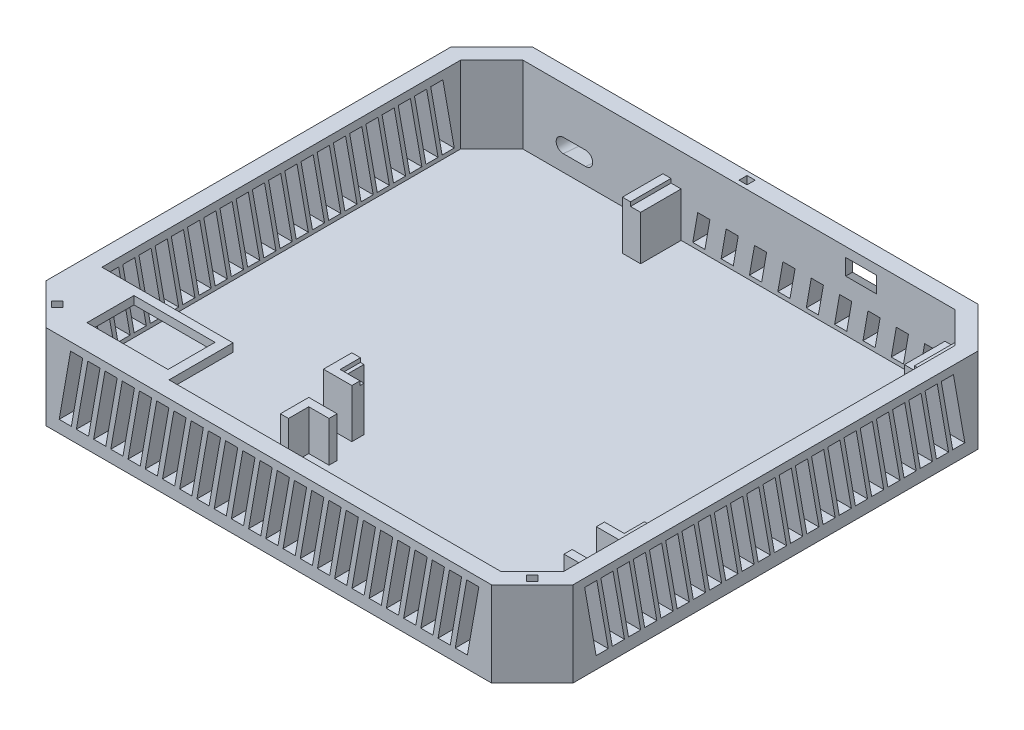
SolidWorks part; units mm, degrees
ref_plane "Front Plane" through (0, 0, 0) normal (0, 0, 1) x (1, 0, 0)
ref_plane "Top Plane" through (0, 0, 0) normal (0, 1, 0) x (1, 0, 0)
ref_plane "Right Plane" through (0, 0, 0) normal (1, 0, 0) x (0, 0, -1)
sketch "Sketch2" plane through (0, 0, 0) normal (0, 1, 0) x (1, 0, 0)
  line L0 (-55, 60) -> (-65, 50)
  line L1 (-55, 60) -> (55, 60)
  line L2 (-65, 50) -> (-65, -50)
  line L3 (-55, -60) -> (55, -60)
  line L4 (65, 50) -> (65, -50)
  line L5 (-65, -50) -> (-55, -60)
  line L6 (55, -60) -> (65, -50)
  line L7 (55, 60) -> (65, 50)
  point P0 (0, 0)
  point P1 (65, -60)
  point P2 (-65, 60)
  point P3 (-65, -60)
  point P4 (65, 60)
  point P14 (0, 60)
  point P15 (65, 0)
  dimension "D1" = 120
  dimension "D2" = 110
extrude "Boss-Extrude1" add sketch "Sketch2" against normal blind 21
shell "Shell3" thickness 4 removed face at (0, 0, 0)
sketch "Sketch3" plane through (0, 0, 0) normal (0, 1, 0) x (1, 0, 0)
  line L0 (55, 60) -> (-55, 60) construction
  line L1 (-1, 59) -> (1, 59)
  line L2 (-1, 59) -> (-1, 57)
  line L3 (-1, 57) -> (1, 57)
  line L4 (1, 59) -> (1, 57)
  line L5 (-1, 59) -> (1, 57) construction
  line L6 (-1, 57) -> (1, 59) construction
  line L7 (53.3431, 56) -> (-53.3431, 56) construction
  line L8 (53.3431, -56) -> (61, -48.3431) construction
  line L9 (57.1716, -53.5858) -> (58.5858, -52.1716)
  line L10 (57.1716, -53.5858) -> (58.5858, -55)
  line L11 (58.5858, -55) -> (60, -53.5858)
  line L12 (58.5858, -52.1716) -> (60, -53.5858)
  line L13 (57.1716, -53.5858) -> (60, -53.5858) construction
  line L14 (58.5858, -55) -> (58.5858, -52.1716) construction
  line L15 (57.1716, -52.1716) -> (60, -55) construction
  line L16 (55, -60) -> (65, -50) construction
  line L17 (0, 60) -> (0, -60) construction
  line L18 (-55, -60) -> (55, -60) construction
  line L19 (-58.5858, -52.1716) -> (-60, -53.5858)
  line L20 (-58.5858, -55) -> (-60, -53.5858)
  line L21 (-57.1716, -53.5858) -> (-58.5858, -52.1716)
  line L22 (-57.1716, -53.5858) -> (-58.5858, -55)
  point P0 (0, 58)
  point P7 (0, 60)
  point P8 (0, 59)
  point P11 (58.5858, -53.5858)
  point P18 (57.8787, -52.8787)
  dimension "D1" = 2
  dimension "D2" = 1
  dimension "D3" = 2
  dimension "D4" = 1
  dimension "D5" = 1
extrude "Cut-Extrude1" cut sketch "Sketch3" against normal blind 2
sketch "Sketch5" plane through (-61, 0, 0) normal (-1, 0, 0) x (0, 0, 1)
  line L0 (-43.9325, -2) -> (-40.9325, -2)
  line L1 (-40.9325, -2) -> (-43.7538, -18)
  line L2 (-43.7538, -18) -> (-46.7538, -18)
  line L3 (-46.7538, -18) -> (-43.9325, -2)
  line L5 (-50, 0) -> (50, 0) construction
  line L7 (-48.3431, -19) -> (-48.3431, 0) construction
  line L8 (-48.3431, -19) -> (48.3431, -19) construction
  point P2 (-45.3431, -10)
  point P11 (-48.3431, -9.5)
  dimension "SLIT_RIGHT_OFFSET" = 3
  dimension "SW" = 3
  dimension "SDS" = 1
  dimension "STS" = 2
  dimension "SA" = 80
extrude "Cut-Extrude3" cut sketch "Sketch5" against normal through all and the other way up to next
pattern_linear "LPattern2" count 23 along (0, 0, 1) of "Cut-Extrude3"
sketch "Sketch4" plane through (0, 0, 56) normal (0, 0, 1) x (1, 0, 0)
  line L0 (-48.9325, -2) -> (-45.9325, -2)
  line L1 (-45.9325, -2) -> (-48.7538, -18)
  line L2 (-48.7538, -18) -> (-51.7538, -18)
  line L3 (-51.7538, -18) -> (-48.9325, -2)
  line L4 (-55, 0) -> (55, 0) construction
  line L7 (-53.3431, -19) -> (53.3431, -19) construction
  line L8 (-53.3431, -19) -> (-53.3431, 0) construction
  point P8 (-50.3431, -10)
  point P11 (-53.3431, -9.5)
  dimension "D1" = 3
  dimension "D2" = 2
  dimension "D3" = 1
  dimension "D4" = 3
  dimension "D5" = 80
extrude "Cut-Extrude2" cut sketch "Sketch4" along normal up to next
pattern_linear "LPattern1" count 24 spacing 4.25 along (1, 0, 0) of "Cut-Extrude2"
sketch "Sketch7" plane through (0, -19, 0) normal (0, 1, 0) x (1, 0, 0)
  line L0 (53.3431, 56) -> (-53.3431, 56) construction
  line L1 (53.3431, 56) -> (-16.7569, 56) construction
  line L2 (53.3431, 56) -> (53.3431, -26.5) construction
  line L3 (53.3431, -26.5) -> (-16.7569, -26.5) construction
  line L4 (-16.7569, 56) -> (-16.7569, -26.5) construction
  line L5 (-18.7569, 56) -> (-18.7569, 46)
  line L6 (-16.878, -20.6506) -> (-15.878, -20.6506)
  line L7 (28.7735, 56) -> (34.3431, 56) construction
  line L8 (28.7735, 56) -> (28.7735, 52.8671) construction
  line L9 (28.7735, 52.8671) -> (34.3431, 52.8671) construction
  line L10 (34.3431, 56) -> (34.3431, 52.8671) construction
  line L11 (28.7735, 56) -> (34.3431, 52.8671) construction
  line L12 (28.7735, 52.8671) -> (34.3431, 56) construction
  line L13 (-18.7569, 46) -> (-14.2569, 46)
  line L16 (-15.878, -20.6506) -> (-15.878, -24.6506)
  line L17 (-15.878, -24.6506) -> (-11.878, -24.6506)
  line L18 (-18.7569, 56) -> (-14.2569, 56)
  line L19 (-14.2569, 56) -> (-14.2569, 46)
  line L20 (-11.878, -24.6506) -> (-11.878, -25.6506)
  line L21 (18.2931, -26.5) -> (18.2931, 56) construction
  line L22 (-18.878, -20.6506) -> (-18.878, -27.6506)
  line L23 (-18.878, -27.6506) -> (-11.878, -27.6506)
  line L24 (-11.878, -27.6506) -> (-11.878, -25.6506)
  line L27 (-16.878, -20.6506) -> (-18.878, -20.6506)
  point P8 (31.5583, 54.4335)
  line M17 (53.3431, 56) -> (-53.3431, 56)
  dimension "D1" = 82.5
  dimension "D2" = 70.1
  dimension "D3" = 3.1329
  dimension "D4" = 5.5696
  dimension "D5" = 19
  dimension "D6" = 2
  dimension "D7" = 2.5
  dimension "D8" = 10
  dimension "D9" = 2
  dimension "D10" = 2
  dimension "D11" = 7
  dimension "D12" = 7
  dimension "D13" = 1
  dimension "D14" = 1
  dimension "D15" = 5.8494
extrude "Boss-Extrude2" add sketch "Sketch7" along normal blind 12 contours L19 L5 L13 M17 | L27 L22 L23 L24 region at (-16.5069, -19, -51) region at (-16.1052, -19, 24.8779)
sketch "Sketch8" plane through (0, -7, 0) normal (0, 1, 0) x (1, 0, 0)
  line L0 (-16.7569, 56) -> (-16.7569, 46)
  line L3 (-16.7569, 46) -> (-14.2569, 46)
  line L4 (-14.2569, 46) -> (-14.2569, 56)
  line L5 (-14.2569, 56) -> (-16.7569, 56)
  line L6 (-16.7569, 56) -> (-16.7569, -26.5) construction
  line L8 (-14.2569, 56) -> (-14.2569, 46) construction
  line L9 (-18.7569, 46) -> (-14.2569, 46) construction
  line L10 (-18.7569, 56) -> (-14.2569, 56) construction
  line L25 (-16.7569, -20.6506) -> (-15.878, -20.6506)
  line L26 (-15.878, -20.6506) -> (-15.878, -24.6506)
  line L27 (-15.878, -24.6506) -> (-11.878, -24.6506)
  line L28 (-11.878, -24.6506) -> (-11.878, -25.6506)
  line L29 (-11.878, -25.6506) -> (-16.7569, -25.6506)
  line L30 (-16.7569, -25.6506) -> (-16.7569, -20.6506)
extrude "Cut-Extrude6" cut sketch "Sketch8" against normal blind 1
ref_plane "Plane3" through (18.2931, 0, 0) normal (-1, 0, 0) x (0, 0, 1)
mirror "Mirror3" about plane through (18.2931, 0, 0) normal (-1, 0, 0) of "Cut-Extrude6", "Boss-Extrude2"
sketch "Sketch9" plane through (0, 0, -56) normal (0, 0, 1) x (1, 0, 0)
  line L0 (53.3431, -7) -> (53.3431, 0) construction
  line L1 (26.3431, -2.34) -> (33.9431, -2.34)
  line L2 (26.3431, -2.34) -> (26.3431, -6.34)
  line L3 (26.3431, -6.34) -> (33.9431, -6.34)
  line L4 (33.9431, -2.34) -> (33.9431, -6.34)
  line L5 (26.3431, -2.34) -> (33.9431, -6.34) construction
  line L6 (26.3431, -6.34) -> (33.9431, -2.34) construction
  line L8 (53.3431, -8) -> (50.8431, -8) construction
  point P0 (30.1431, -4.34)
  dimension "D1" = 4
  dimension "D2" = 7.6
  dimension "D3" = 19.4
  dimension "D4" = 1.66
extrude "Cut-Extrude7" cut sketch "Sketch9" against normal up to next (4 mm away) draft 30 draft outward yes
sketch "Sketch10" plane through (0, -19, 0) normal (0, 1, 0) x (1, 0, 0)
  line L0 (53.3431, -35.5) -> (53.3431, -33.5)
  line L1 (53.3431, -35.5) -> (53.3431, -54) construction
  line L2 (53.3431, -35.5) -> (-14.6569, -35.5) construction
  line L3 (-14.6569, -35.5) -> (-14.6569, -54) construction
  line L4 (53.3431, -54) -> (-14.6569, -54) construction
  line L5 (53.3431, -33.5) -> (48.3431, -33.5)
  line L6 (48.3431, -33.5) -> (48.3431, -35.5)
  line L7 (48.3431, -35.5) -> (53.3431, -35.5)
  line L8 (53.3431, -44.75) -> (-14.6569, -44.75) construction
  line L9 (19.3431, -35.5) -> (19.3431, -54) construction
  line L10 (48.3431, -56) -> (48.3431, -54)
  line L11 (48.3431, -54) -> (53.3431, -54)
  line L12 (53.3431, -56) -> (48.3431, -56)
  line L13 (53.3431, -54) -> (53.3431, -56)
  line L14 (-9.6569, -56) -> (-9.6569, -54)
  line L18 (-9.6569, -54) -> (-14.6569, -54)
  line L19 (-9.6569, -35.5) -> (-14.6569, -35.5)
  line L20 (-16.6569, -33.5) -> (-9.6569, -33.5)
  line L21 (-9.6569, -33.5) -> (-9.6569, -35.5)
  line L22 (-53.3431, -56) -> (53.3431, -56) construction
  line L24 (-16.6569, -33.5) -> (-16.6569, -40.5)
  line L25 (-14.6569, -35.5) -> (-14.6569, -40.5)
  line L26 (-14.6569, -40.5) -> (-16.6569, -40.5)
  line L27 (-16.6569, -56) -> (-16.6569, -49)
  line L28 (-9.6569, -56) -> (-16.6569, -56)
  line L29 (-14.6569, -49) -> (-16.6569, -49)
  line L30 (-14.6569, -54) -> (-14.6569, -49)
  dimension "D3" = 2
  dimension "D1" = 68
  dimension "D2" = 18.5
  dimension "D4" = 2
  dimension "D5" = 7
  dimension "D6" = 2
  dimension "D7" = 5
  dimension "D8" = 7
extrude "Boss-Extrude3" add sketch "Sketch10" along normal blind 10
sketch "Sketch12" plane through (0, 0, 0) normal (0, 1, 0) x (1, 0, 0)
  line L0 (-53.3431, -56) -> (-28.6431, -56)
  line L1 (-53.3431, -56) -> (-16.6569, -56) construction
  line L2 (-28.6431, -56) -> (-28.6431, -40.2)
  line L3 (-28.6431, -40.2) -> (-61, -40.2)
  line L4 (-61, 48.3431) -> (-61, -48.3431) construction
  line L5 (-61, -40.2) -> (-61, -48.3431)
  line L6 (-61, -48.3431) -> (-53.3431, -56)
  line L8 (-50.9931, -42.3) -> (-30.9931, -42.3)
  line L9 (-50.9931, -42.3) -> (-50.9931, -53.9)
  line L10 (-50.9931, -53.9) -> (-30.9931, -53.9)
  line L11 (-30.9931, -42.3) -> (-30.9931, -53.9)
  line L12 (-50.9931, -42.3) -> (-30.9931, -53.9) construction
  line L13 (-50.9931, -53.9) -> (-30.9931, -42.3) construction
  point P9 (-40.9931, -48.1)
  point P16 (-30.9931, -48.1)
  point P17 (-28.6431, -48.1)
  point P18 (-40.9931, -53.9)
  point P19 (-40.9931, -56)
  dimension "D1" = 24.7
  dimension "D2" = 15.8
  dimension "D3" = 11.6
  dimension "D4" = 20
extrude "Boss-Extrude4" add sketch "Sketch12" against normal up to vertex (2 mm away) up to point (-28.9325, -2, 56)
sketch "Sketch13" plane through (0, 0, -56) normal (0, 0, 1) x (1, 0, 0)
  line L0 (-43.3431, -13.25) -> (-37.8431, -13.25) construction
  line L1 (-43.3431, -11.5) -> (-37.8431, -11.5)
  line L2 (-43.3431, -15) -> (-37.8431, -15)
  line L3 (-18.7569, -19) -> (-53.3431, -19) construction
  line L4 (-53.3431, -19) -> (-53.3431, 0) construction
  arc A0 (-43.3431, -11.5) -> (-43.3431, -15) centre (-43.3431, -13.25) ccw
  arc A1 (-37.8431, -15) -> (-37.8431, -11.5) centre (-37.8431, -13.25) ccw
  point P2 (-40.5931, -13.25)
  point P7 (-45.0931, -13.25)
  point P8 (-36.0931, -13.25)
  dimension "D4" = 10
  dimension "D1" = 9
  dimension "D2" = 3.5
  dimension "D3" = 4
extrude "Cut-Extrude9" cut sketch "Sketch13" against normal up to next (4 mm away) draft 5 draft outward yes
sketch "Sketch14" plane through (0, 0, -56) normal (0, 0, -1) x (-1, 0, 0)
  line L0 (-48.8431, -11) -> (-47.6089, -18)
  line L1 (-47.6089, -18) -> (-44.6089, -18)
  line L2 (-44.6089, -18) -> (-45.8431, -11)
  line L3 (-45.8431, -11) -> (-48.8431, -11)
  line L7 (-50.8431, -19) -> (14.2569, -19) construction
  line L8 (-50.8431, -8) -> (-50.8431, -19) construction
  dimension "D1" = 80
  dimension "D2" = 7
  dimension "D3" = 3
  dimension "D4" = 2
  dimension "D5" = 1
extrude "Cut-Extrude10" cut sketch "Sketch14" along normal up to next
pattern_linear "LPattern3" count 9 spacing 7 along (-1, 0, 0) of "Cut-Extrude10"
sketch "Sketch15" plane through (0, -19, 0) normal (0, 1, 0) x (1, 0, 0)
  line L0 (-9.2569, 52) -> (-9.2569, 49)
  line L1 (-9.2569, 49) -> (45.8431, 39.2844)
  line L2 (45.8431, 39.2844) -> (45.8431, 42.2844)
  line L3 (45.8431, 42.2844) -> (-9.2569, 52)
  line L4 (-9.4528, -38.5) -> (-6.4528, -38.5)
  line L5 (-6.4528, -38.5) -> (-8.6569, -51)
  line L6 (-8.6569, -51) -> (-11.6569, -51)
  line L7 (-11.6569, -51) -> (-9.4528, -38.5)
  line L8 (-52.8146, 45.373) -> (-52.8146, 42.373)
  line L9 (-52.8146, 42.373) -> (-32.8146, 38.8464)
  line L10 (-32.8146, 38.8464) -> (-32.8146, 41.8464)
  line L11 (-32.8146, 41.8464) -> (-52.8146, 45.373)
  line L12 (-14.6569, -54) -> (-14.6569, -49) construction
  line L13 (-9.2569, 52) -> (45.8431, 52) construction
  line L14 (-9.2569, 52) -> (-9.2569, -23.6506) construction
  line L15 (-9.2569, -23.6506) -> (45.8431, -23.6506) construction
  line L16 (45.8431, 52) -> (45.8431, -23.6506) construction
  line L17 (-11.6569, -38.5) -> (50.3431, -38.5) construction
  line L18 (-11.6569, -38.5) -> (-11.6569, -51) construction
  line L19 (-11.6569, -51) -> (50.3431, -51) construction
  line L20 (50.8431, 56) -> (-14.2569, 56) construction
  line L21 (-18.878, -27.6506) -> (-11.878, -27.6506) construction
  line L22 (50.8431, 56) -> (50.8431, 46) construction
  line L23 (50.3431, -38.5) -> (50.3431, -51) construction
  line L24 (-9.6569, -54) -> (-14.6569, -54) construction
  line L25 (-14.6569, -35.5) -> (-9.6569, -35.5) construction
  line L26 (53.3431, -35.5) -> (53.3431, -33.5) construction
  point P10 (18.2931, 56)
  point P18 (18.2931, 52)
  dimension "D1" = 3
  dimension "D2" = 20
  dimension "D3" = 80
  dimension "D4" = 80
  dimension "D5" = 4
  dimension "D6" = 5
  dimension "D7" = 3
  dimension "D8" = 4
  dimension "D9" = 3
  dimension "D10" = 3
  dimension "D11" = 3
extrude "Cut-Extrude11" [suppressed] cut sketch "Sketch15" against normal up to next
